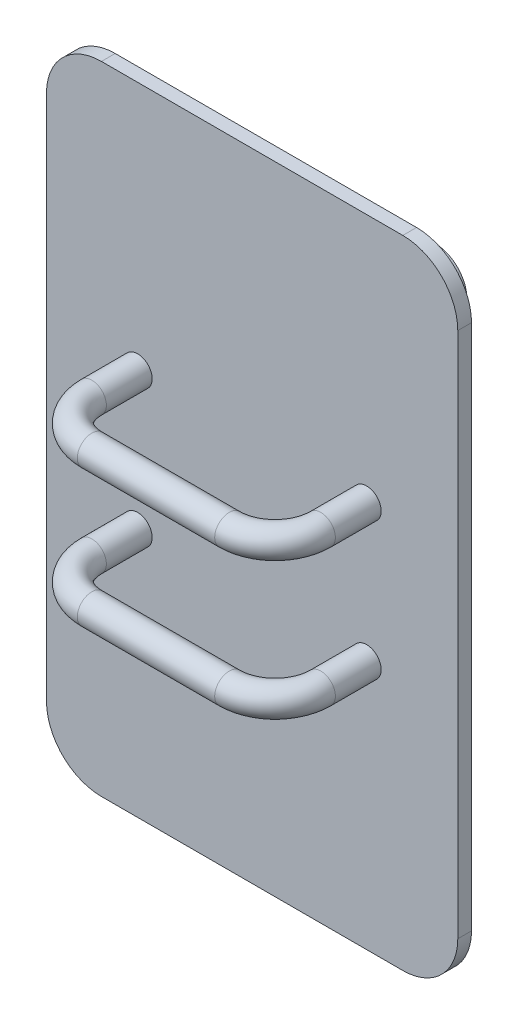
SolidWorks part; units mm, degrees
ref_plane "Front Plane" through (0, 0, 0) normal (0, 0, 1) x (1, 0, 0)
ref_plane "Top Plane" through (0, 0, 0) normal (0, 1, 0) x (1, 0, 0)
ref_plane "Right Plane" through (0, 0, 0) normal (1, 0, 0) x (0, 0, -1)
sketch "Sketch1" plane through (0, 0, 0) normal (0, 0, 1) x (1, 0, 0)
  line L0 (-131.5265, -25.8333) -> (-50.7265, -25.8333) construction
  line L1 (-131.5265, 39.1667) -> (-50.7265, 39.1667) construction
  line L2 (-131.5265, 39.1667) -> (-131.5265, -90.8333) construction
  line L3 (-131.5265, -90.8333) -> (-50.7265, -90.8333) construction
  line L4 (-50.7265, 39.1667) -> (-50.7265, -90.8333) construction
  line L5 (-91.1265, 39.1667) -> (-91.1265, -90.8333) construction
  line L6 (-131.0265, 38.6667) -> (-51.2265, 38.6667)
  line L7 (-51.2265, 38.6667) -> (-51.2265, -90.3333)
  line L8 (-131.0265, -90.3333) -> (-51.2265, -90.3333)
  line L9 (-131.0265, 38.6667) -> (-131.0265, -90.3333)
  line L13 (-131.5265, 39.1667) -> (-50.7265, 39.1667) construction
  line L16 (-50.7265, 39.1667) -> (-50.7265, -90.8333) construction
  dimension "D1" = 0.5
extrude "Boss-Extrude1" add sketch "Sketch1" along normal blind 4
fillet "Fillet1" radius 7 4 edges at (-51.2265, -90.3333, 2) (-131.0265, -90.3333, 2) (-131.0265, 38.6667, 2) (-51.2265, 38.6667, 2)
sketch "Sketch2" plane through (0, 0, 0) normal (0, 0, -1) x (-1, 0, 0)
  line L0 (51.2265, -25.8333) -> (131.0265, -25.8333)
  line L4 (51.2265, 31.6667) -> (51.2265, -83.3333)
  line L5 (58.2265, -90.3333) -> (124.0265, -90.3333)
  line L6 (131.0265, -83.3333) -> (131.0265, 31.6667)
  line L7 (124.0265, 38.6667) -> (58.2265, 38.6667)
  line L8 (51.2265, 31.6667) -> (51.2265, -83.3333)
  line L9 (58.2265, -90.3333) -> (124.0265, -90.3333)
  line L10 (131.0265, -83.3333) -> (131.0265, 31.6667)
  line L11 (124.0265, 38.6667) -> (58.2265, 38.6667)
  circle A0 centre (91.1265, -85.8333) radius 3.325 construction
  circle A1 centre (126.5265, -56.5833) radius 3.325 construction
  circle A2 centre (126.5265, 1.9167) radius 3.325 construction
  circle A3 centre (55.7265, -56.5833) radius 3.325 construction
  arc A4 (51.2265, -83.3333) -> (58.2265, -90.3333) centre (58.2265, -83.3333) ccw
  arc A5 (124.0265, -90.3333) -> (131.0265, -83.3333) centre (124.0265, -83.3333) ccw
  arc A6 (131.0265, 31.6667) -> (124.0265, 38.6667) centre (124.0265, 31.6667) ccw
  arc A7 (58.2265, 38.6667) -> (51.2265, 31.6667) centre (58.2265, 31.6667) ccw
  arc A8 (51.2265, -83.3333) -> (58.2265, -90.3333) centre (58.2265, -83.3333) ccw
  arc A9 (124.0265, -90.3333) -> (131.0265, -83.3333) centre (124.0265, -83.3333) ccw
  arc A10 (131.0265, 31.6667) -> (124.0265, 38.6667) centre (124.0265, 31.6667) ccw
  arc A11 (58.2265, 38.6667) -> (51.2265, 31.6667) centre (58.2265, 31.6667) ccw
  circle A12 centre (55.7265, 1.9167) radius 3.325 construction
  circle A13 centre (91.1265, -85.8333) radius 3.325
  circle A14 centre (126.5265, -56.5833) radius 3.325
  circle A15 centre (126.5265, 1.9167) radius 3.325
  circle A16 centre (55.7265, -56.5833) radius 3.325
  circle A17 centre (55.7265, 1.9167) radius 3.325
  circle A18 centre (91.1265, 34.1667) radius 3.325
  dimension "D1" = 0
extrude "Cut-Extrude2" cut sketch "Sketch2" against normal blind 3.2 contours A17 | A18 | A16 | A13 | A15 | A14 region at (-91.1265, -85.8333, 0) region at (-55.7265, -56.5833, 0) region at (-55.7265, 1.9167, 0) region at (-91.1265, 34.1667, 0)
sketch "Sketch3" plane through (0, 0, 4) normal (0, 0, 1) x (1, 0, 0)
  line L0 (-124.0265, -95.3333) -> (-58.2265, -95.3333)
  line L1 (-46.2265, -83.3333) -> (-46.2265, 31.6667)
  line L2 (-58.2265, 43.6667) -> (-124.0265, 43.6667)
  line L3 (-136.0265, 31.6667) -> (-136.0265, -83.3333)
  line L4 (-124.0265, -90.3333) -> (-58.2265, -90.3333)
  line L5 (-51.2265, -83.3333) -> (-51.2265, 31.6667)
  line L6 (-58.2265, 38.6667) -> (-124.0265, 38.6667)
  line L7 (-131.0265, 31.6667) -> (-131.0265, -83.3333)
  line L8 (-124.0265, -90.3333) -> (-58.2265, -90.3333)
  line L9 (-51.2265, -83.3333) -> (-51.2265, 31.6667)
  line L10 (-58.2265, 38.6667) -> (-124.0265, 38.6667)
  line L11 (-131.0265, 31.6667) -> (-131.0265, -83.3333)
  arc A0 (-58.2265, -95.3333) -> (-46.2265, -83.3333) centre (-58.2265, -83.3333) ccw
  arc A1 (-46.2265, 31.6667) -> (-58.2265, 43.6667) centre (-58.2265, 31.6667) ccw
  arc A2 (-124.0265, 43.6667) -> (-136.0265, 31.6667) centre (-124.0265, 31.6667) ccw
  arc A3 (-136.0265, -83.3333) -> (-124.0265, -95.3333) centre (-124.0265, -83.3333) ccw
  arc A4 (-58.2265, -90.3333) -> (-51.2265, -83.3333) centre (-58.2265, -83.3333) ccw
  arc A5 (-51.2265, 31.6667) -> (-58.2265, 38.6667) centre (-58.2265, 31.6667) ccw
  arc A6 (-124.0265, 38.6667) -> (-131.0265, 31.6667) centre (-124.0265, 31.6667) ccw
  arc A7 (-131.0265, -83.3333) -> (-124.0265, -90.3333) centre (-124.0265, -83.3333) ccw
  arc A8 (-58.2265, -90.3333) -> (-51.2265, -83.3333) centre (-58.2265, -83.3333) ccw
  arc A9 (-51.2265, 31.6667) -> (-58.2265, 38.6667) centre (-58.2265, 31.6667) ccw
  arc A10 (-124.0265, 38.6667) -> (-131.0265, 31.6667) centre (-124.0265, 31.6667) ccw
  arc A11 (-131.0265, -83.3333) -> (-124.0265, -90.3333) centre (-124.0265, -83.3333) ccw
  line M9 (-124.0265, -90.3333) -> (-58.2265, -90.3333)
  arc M10 (-58.2265, -90.3333) -> (-51.2265, -83.3333) centre (-58.2265, -83.3333) ccw
  line M11 (-51.2265, -83.3333) -> (-51.2265, 31.6667)
  arc M12 (-51.2265, 31.6667) -> (-58.2265, 38.6667) centre (-58.2265, 31.6667) ccw
  line M13 (-58.2265, 38.6667) -> (-124.0265, 38.6667)
  arc M14 (-124.0265, 38.6667) -> (-131.0265, 31.6667) centre (-124.0265, 31.6667) ccw
  line M15 (-131.0265, 31.6667) -> (-131.0265, -83.3333)
  arc M16 (-131.0265, -83.3333) -> (-124.0265, -90.3333) centre (-124.0265, -83.3333) ccw
  dimension "D1" = 0
  dimension "D2" = 5
extrude "Boss-Extrude3" add sketch "Sketch3" along normal blind 3 contours M16 M9 M10 M11 M12 M13 M14 M15 | L3 A3 L0 A0 L1 A1 L2 A2 M9 M16 M15 M14 M13 M12 M11 M10 | L8 A8 L9 A9 L10 A10 L11 A11 | L0 A0 L1 A1 L2 A2 L3 A3 region at (-131.3416, -90.6485, 4) region at (-91.1265, -25.8333, 4)
sketch "Sketch6" plane through (0, 0, 7) normal (0, 0, 1) x (1, 0, 0)
  line L0 (-91.1265, 43.6667) -> (-91.1265, -95.3333) construction
  line L1 (-58.2265, 43.6667) -> (-124.0265, 43.6667) construction
  line L2 (-124.0265, -95.3333) -> (-58.2265, -95.3333) construction
  line L3 (-136.0265, -25.8333) -> (-46.2265, -25.8333) construction
  line L4 (-136.0265, 31.6667) -> (-136.0265, -83.3333) construction
  line L5 (-46.2265, -83.3333) -> (-46.2265, 31.6667) construction
  line L7 (-116.1265, -40.8333) -> (-66.1265, -40.8333) construction
  line L8 (-116.1265, -40.8333) -> (-116.1265, -10.8333) construction
  line L9 (-116.1265, -10.8333) -> (-66.1265, -10.8333) construction
  line L10 (-66.1265, -40.8333) -> (-66.1265, -10.8333) construction
  line L11 (-116.1265, -40.8333) -> (-66.1265, -10.8333) construction
  line L12 (-116.1265, -10.8333) -> (-66.1265, -40.8333) construction
  circle A0 centre (-116.1265, -10.8333) radius 3.175
  circle A1 centre (-66.1265, -10.8333) radius 3.175
  circle A2 centre (-66.1265, -40.8333) radius 3.175
  circle A3 centre (-116.1265, -40.8333) radius 3.175
  point P12 (-91.1265, -25.8333)
  point P21 (0, 0)
  dimension "D3" = 6.35
  dimension "D1" = 30
  dimension "D2" = 50
sketch3d "3DSketch3"
  line L0 (-116.1265, -10.8333, 7) -> (-116.1265, -10.8333, 17)
  line L2 (-116.1265, -10.8333, 27) -> (-116.1265, -10.8333, 7)
  line L3 (-106.1265, -10.8333, 27) -> (-76.1265, -10.8333, 27)
  line L4 (-66.1265, -10.8333, 17) -> (-66.1265, -10.8333, 7)
  line L5 (-116.1265, -10.8333, 7) -> (-66.1265, -10.8333, 7)
  line L6 (-116.1265, -40.8333, 7) -> (-116.1265, -40.8333, 17)
  line L8 (-116.1265, -40.8333, 27) -> (-116.1265, -40.8333, 7)
  line L9 (-106.1265, -40.8333, 27) -> (-76.1265, -40.8333, 27)
  line L10 (-66.1265, -40.8333, 17) -> (-66.1265, -40.8333, 7)
  line L11 (-116.1265, -40.8333, 7) -> (-66.1265, -40.8333, 7)
  arc A0 (-66.1265, -10.8333, 17) -> (-76.1265, -10.8333, 27) centre (-76.1265, -10.8333, 17) ccw
  arc A1 (-116.1265, -10.8333, 17) -> (-106.1265, -10.8333, 27) centre (-106.1265, -10.8333, 17) ccw
  arc A2 (-66.1265, -40.8333, 17) -> (-76.1265, -40.8333, 27) centre (-76.1265, -40.8333, 17) ccw
  arc A3 (-106.1265, -40.8333, 27) -> (-116.1265, -40.8333, 17) centre (-106.1265, -40.8333, 17) ccw
  point P8 (-66.1265, -10.8333, 27)
  point P9 (-76.1265, -20.8333, 17)
  point P12 (-116.1265, -10.8333, 27)
  point P14 (-106.1265, -0.8333, 17)
  point P23 (-66.1265, -40.8333, 27)
  point P24 (-76.1265, -50.8333, 17)
  point P27 (-116.1265, -40.8333, 27)
  point P29 (-106.1265, -50.8333, 17)
  dimension "D2" = 10
  dimension "D4" = 10
  dimension "D1" = 20
  dimension "D3" = 20
sweep "Sweep1" add profiles "Sketch6" path "3DSketch3"
